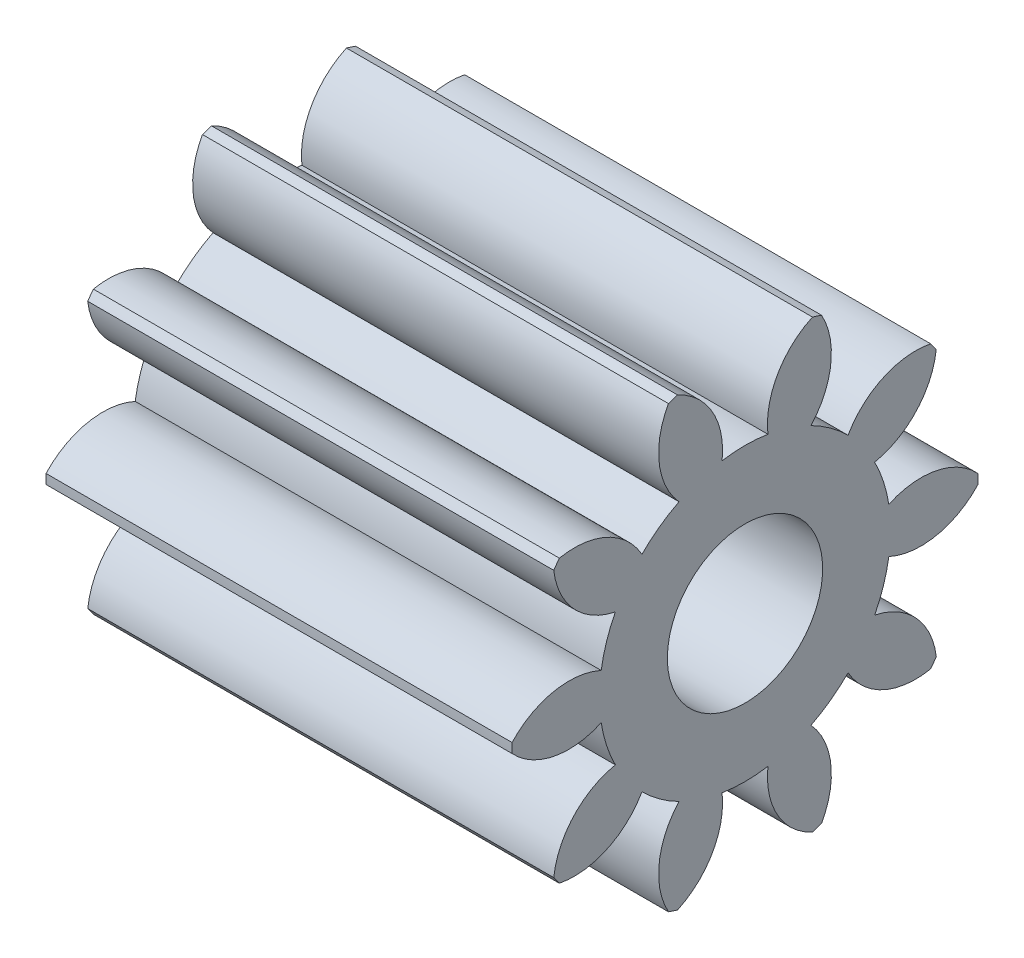
SolidWorks part; units mm, degrees
ref_plane "Plane1" through (0, 0, 0) normal (0, 0, 1) x (1, 0, 0)
ref_plane "Plane2" through (0, 0, 0) normal (0, 1, 0) x (1, 0, 0)
ref_plane "Plane3" through (0, 0, 0) normal (1, 0, 0) x (0, 0, -1)
other "Configuration Table"
sketch "HoldingSke" plane through (0, 0, 0) normal (0, 1, 0) x (1, 0, 0)
  line L0 (0, 0) -> (0.7878, -0.1389)
  line L1 (-15, 0) -> (100, 0) construction
  line L2 (0, 0) -> (-2.1039, 2.3779)
  line L3 (0, 0) -> (-11.863, 4.5341)
  line L4 (0, 0) -> (8.5048, 1.4996)
  line L5 (0, 0) -> (-46.8476, -17.4728)
  line L6 (0, 0) -> (-12.4344, -8.3896)
  line L7 (-2.1039, 2.3779) -> (8.6586, 51.2059)
  line L8 (-76.2, 54.61) -> (-75.3, 54.61)
  line L9 (-71.009, 38.7566) -> (-53.1078, 45.2721)
  line L10 (-76.2, 71.12) -> (104.1128, 71.12)
  line L11 (0, 0) -> (-15, 0)
  line L12 (-76.2, 101.6) -> (-76.155, 101.6)
  line L13 (24.9733, 27.94) -> (52.9518, 28.4284)
  line L14 (24.9733, 27.94) -> (24.9743, 27.94)
  line L15 (24.9733, 27.94) -> (100.4006, 29.5858)
  line L16 (-63.627, -1.25) -> (-12.827, -1.25)
  circle A0 centre (0, 0) radius 2.5
  circle A1 centre (0, 0) radius 4.6865
  circle A2 centre (0, 0) radius 37.5
  circle A3 centre (0, 0) radius 2.5
  dimension "Num_teeth" = 10
  dimension "Pitch_radius" = 180.3128
  dimension "Width" = 15
  dimension "Thickness" = 15
sketch "BasProSke" plane through (0, 0, 0) normal (0, 1, 0) x (1, 0, 0)
  line L0 (-10, 0) -> (60, 0) construction
  line L1 (0, 0) -> (0, 7.5)
  line L2 (0, 0) -> (15, 0)
  line L3 (15, 0) -> (15, 7.5)
  line L4 (15, 7.5) -> (0, 7.5)
  dimension "Thickness" = 15
  dimension "Diameter" = 15
revolve "Base-Revolve" add sketch "BasProSke" angle 360 about L0
sketch "TooCutSke" plane through (0, 0, 0) normal (1, 0, 0) x (0, 0, -1)
  line L1 (0, 0) -> (0, 107) construction
  line L2 (0, 0) -> (-1.0563, 6.1601) construction
  line L3 (0, 0) -> (-3.8225, 11.7646) construction
  line L4 (-1.0563, 6.1601) -> (-1.9113, 5.8823) construction
  arc A0 (0.7377, 4.6281) -> (-0.7377, 4.6281) centre (0, 0) ccw
  arc A1 (2.2058, 7.1949) -> (-2.2058, 7.1949) centre (0, 0) ccw
  circle A2 centre (0, 0) radius 6.25 construction
  circle A3 centre (0, 0) radius 5.8731 construction
  arc A4 (-0.7377, 4.6281) -> (-2.2058, 7.1949) centre (-3.2217, 4.9106) ccw
  arc A5 (2.2058, 7.1949) -> (0.7377, 4.6281) centre (3.2217, 4.9106) ccw
extrude "ToothCut" cut sketch "TooCutSke" along normal through all
fillet "Breaks" [suppressed] radius 0.025 tangent propagation no
fillet "RootFillets" [suppressed] radius 0.3135
pattern_circular "TeethCuts" count 10 every 36 about axis through (-10, 0, 0) along (1, 0, 0) of "ToothCut", "RootFillets", "Breaks"
sketch "HubNeaOneSke" plane through (0, 0, 0) normal (-1, 0, 0) x (0, 0, 1)
  circle A0 centre (0, 0) radius 4.6865
  dimension "Diameter" = 9.373
extrude "HubNearOne" [suppressed] add sketch "HubNeaOneSke" along normal blind 35.0001
sketch "HubNeaBotSke" plane through (0, 0, 0) normal (-1, 0, 0) x (0, 0, 1)
  circle A0 centre (0, 0) radius 4.6865
  dimension "Diameter" = 9.373
extrude "HubNearBoth" [suppressed] add sketch "HubNeaBotSke" along normal blind 17.5
ref_plane "FarPln" through (15, 0, 0) normal (1, 0, 0) x (0, 0, -1)
sketch "HubFarSke" plane through (15, 0, 0) normal (1, 0, 0) x (0, 0, -1)
  circle A0 centre (0, 0) radius 4.6865
  dimension "Diameter" = 9.373
extrude "HubFar" [suppressed] add sketch "HubFarSke" along normal blind 17.5
sketch "BorSke" plane through (0, 0, 0) normal (1, 0, 0) x (0, 0, -1)
  circle A0 centre (0, 0) radius 2.5
  dimension "Diameter" = 5
extrude "Bore" cut sketch "BorSke" along normal mid plane 100.0001
sketch "KeySke" plane through (0, 0, 0) normal (1, 0, 0) x (0, 0, -1)
  line L0 (-1, 0) -> (-1, 3.4)
  line L1 (-1, 3.4) -> (1, 3.4)
  line L2 (1, 3.4) -> (1, 0)
  line L3 (0, 0) -> (0, 34) construction
  line L4 (-1, 0) -> (1, 0)
extrude "Keyway" [suppressed] cut sketch "KeySke" along normal mid plane 100.0001
pattern_circular "Keyway2" [suppressed] count 2 every 90 about axis through (-10, 0, 0) along (1, 0, 0)
equation "' \"Module@HoldingSke\" = 6.35"
equation "' \"Num_teeth@HoldingSke\" = 12"
equation "' \"Ap@HoldingSke\" =  20"
equation "' \"Ap@HoldingSke\" = 20"
equation "' \"Width@HoldingSke\" = 0.5 * 25.4"
equation "' \"Hub_dia@HoldingSke\"= 1 * 25.4"
equation "' \"Hub_dia@HoldingSke\" = 1 * 25.4"
equation "' \"Overall_len@HoldingSke\" = 1.0 * 25.4"
equation "' \"Bore@HoldingSke\" = 0.75 * 25.4"
equation "' \"T_dim@HoldingSke\" = 0.1 * 25.4"
equation "' \"Width@KeySke\" = 0.25 * 25.4"
equation "' \"Show_teeth@HoldingSke\" = 13"
equation "' \"Backlash@HoldingSke\" = 0.009 * 25.4"
equation "' \"Addendum_fac@HoldingSke\" = 1.0"
equation "' \"Dedendum_fac@HoldingSke\" = 1.25"
equation "' \"Dedendum_add@HoldingSke\" = 0.00005 * 25.4"
equation "' \"Clearance_fac@HoldingSke\" = 0.25"
equation "\"Pitch@HoldingSke\" = 1 / \"Module@HoldingSke\""
equation "\"Overcut_dia@TooCutSke\" = (\"Num_teeth@HoldingSke\" + 2 * \"Addendum_fac@HoldingSke\") / \"Pitch@HoldingSke\" + 0.002 * 25.4"
equation "\"Pitch_dia@TooCutSke\" = \"Num_teeth@HoldingSke\" / \"Pitch@HoldingSke\""
equation "\"Base_dia@TooCutSke\" = \"Num_teeth@HoldingSke\" / \"Pitch@HoldingSke\" * cos((\"Ap@HoldingSke\"  * 3.14159265 / 180))"
equation "\"Root_dia@TooCutSke\" = (\"Num_teeth@HoldingSke\" + 2) / \"Pitch@HoldingSke\" - 2 * (\"Addendum_fac@HoldingSke\" + \"Dedendum_fac@HoldingSke\") / \"Pitch@HoldingSke\" - \"Dedendum_add@HoldingSke\" * 2"
equation "\"Half_ang@TooCutSke\" = 180 / \"Num_teeth@HoldingSke\""
equation "\"Half_CT@TooCutSke\" = \"Num_teeth@HoldingSke\" / \"Pitch@HoldingSke\" * sin((3.14159265 / 2 / \"Num_teeth@HoldingSke\")) / 2 - 7 * \"Backlash@HoldingSke\" / 4"
equation "\"Flank_rad@TooCutSke\" = \"Num_teeth@HoldingSke\" / \"Pitch@HoldingSke\" / 5"
equation "\"Radius@RootFillets\" = \"Clearance_fac@HoldingSke\" / \"Pitch@HoldingSke\" + \"Dedendum_add@HoldingSke\""
equation "\"Break_rad@Breaks\" = 0.02 / \"Pitch@HoldingSke\""
equation "\"Thickness@HoldingSke\" = \"Width@HoldingSke\""
equation "\"OAL@HoldingSke\" = \"Thickness@HoldingSke\""
equation "\"MHD@HoldingSke\" = (\"Num_teeth@HoldingSke\" + 2) / \"Pitch@HoldingSke\" - 2 * (\"Addendum_fac@HoldingSke\" + \"Dedendum_fac@HoldingSke\")  / \"Pitch@HoldingSke\" - \"Dedendum_add@HoldingSke\" * 2"
equation "\"MBD@HoldingSke\" = (\"Num_teeth@HoldingSke\" + 2) / \"Pitch@HoldingSke\" - 2 * (\"Addendum_fac@HoldingSke\" + \"Dedendum_fac@HoldingSke\")  / \"Pitch@HoldingSke\" - \"Dedendum_add@HoldingSke\" * 2 - 0.002 * 25.4"
equation "\"MHD@HoldingSke\" = ((sgn( \"MHD@HoldingSke\" - \"Hub_dia@HoldingSke\" )-1)*( \"MHD@HoldingSke\" - \"Hub_dia@HoldingSke\" ))/-2+ \"Hub_dia@HoldingSke\""
equation "\"MBD@HoldingSke\" = ((sgn( \"MBD@HoldingSke\" - \"Bore@HoldingSke\" )-1)*( \"MBD@HoldingSke\" - \"Bore@HoldingSke\" ))/-2+ \"Bore@HoldingSke\""
equation "\"OAL@HoldingSke\" = ((sgn( \"OAL@HoldingSke\" - \"Overall_len@HoldingSke\" )+1)*( \"OAL@HoldingSke\" - \"Overall_len@HoldingSke\" ))/2 + \"Overall_len@HoldingSke\" + 0.000002 * 25.4"
equation "\"Num_teeth@TeethCuts\" = int( \"Show_teeth@HoldingSke\" ) + 1"
equation "\"Num_teeth@TeethCuts\" = ((sgn( \"Num_teeth@TeethCuts\" - \"Num_teeth@HoldingSke\" )-1)*( \"Num_teeth@TeethCuts\" - \"Num_teeth@HoldingSke\" ))/-2+ \"Num_teeth@HoldingSke\""
equation "\"Num_teeth@TeethCuts\" = ((sgn( \"Num_teeth@TeethCuts\" - 2.0)+1)*( \"Num_teeth@TeethCuts\" - 2.0))/2 +2.0"
equation "\"Angle@TeethCuts\" = 360.0 / \"Num_teeth@HoldingSke\""
equation "\"Diameter@BasProSke\" = (\"Num_teeth@HoldingSke\" + 2 * \"Addendum_fac@HoldingSke\") / \"Pitch@HoldingSke\""
equation "\"Thickness@BasProSke\"  = \"Thickness@HoldingSke\""
equation "' \"Fillet_rad@BasProSke\" =  \"Thickness@HoldingSke\" * 0.05"
equation "' \"Fillet_rad@BasProSke\" = \"Thickness@HoldingSke\" * 0.05"
equation "\"MHD@HoldingSke\" = ((sgn( \"MHD@HoldingSke\" - \"Root_dia@TooCutSke\" )-1)*( \"MHD@HoldingSke\" - \"Root_dia@TooCutSke\" ))/-2+ \"Root_dia@TooCutSke\""
equation "\"Diameter@HubNeaOneSke\" = \"MHD@HoldingSke\""
equation "\"Length@HubNearOne\" = \"OAL@HoldingSke\" - \"Thickness@BasProSke\""
equation "\"Diameter@HubNeaBotSke\" = \"MHD@HoldingSke\""
equation "\"Length@HubNearBoth\" = ( \"OAL@HoldingSke\" - \"Thickness@BasProSke\" ) / 2.0"
equation "\"Thickness@FarPln\" = \"Thickness@BasProSke\""
equation "\"Diameter@HubFarSke\" = \"MHD@HoldingSke\""
equation "\"Length@HubFar\" = ( \"OAL@HoldingSke\" - \"Thickness@BasProSke\" ) / 2.0"
equation "\"Diameter@BorSke\" = \"MBD@HoldingSke\""
equation "\"D1@Bore\" = \"OAL@HoldingSke\" * 2.0"
equation "\"D1@Keyway\" = \"OAL@HoldingSke\" * 2.0"
equation "\"Offset@KeySke\" = \"T_dim@HoldingSke\" + \"MBD@HoldingSke\" / 2.0"
